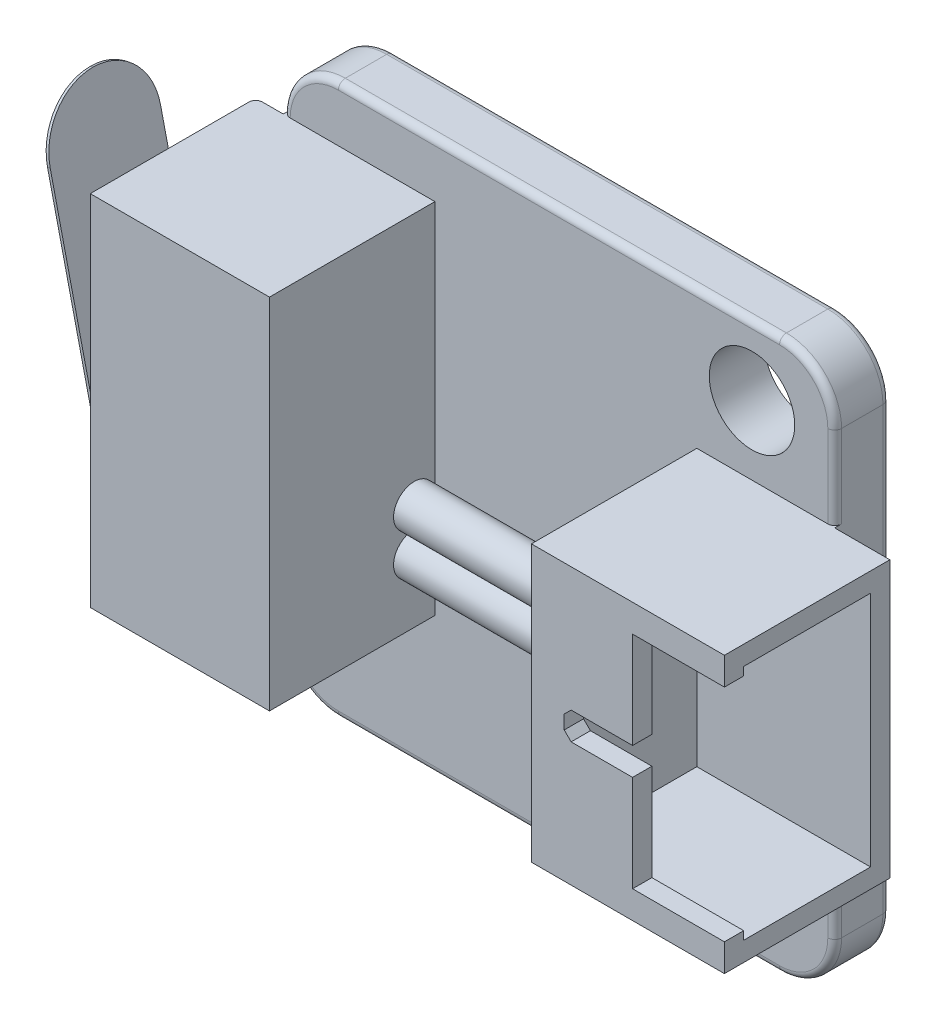
SolidWorks part; units mm, degrees
ref_plane "Alzado" through (0, 0, 0) normal (0, 0, 1) x (1, 0, 0)
ref_plane "Planta" through (0, 0, 0) normal (0, 1, 0) x (1, 0, 0)
ref_plane "Vista lateral" through (0, 0, 0) normal (1, 0, 0) x (0, 0, -1)
ref_plane "Plano1" through (0, 0, 2) normal (0, 0, 1) x (1, 0, 0)
sketch "Croquis1" plane through (0, 0, 2) normal (0, 0, 1) x (1, 0, 0)
  line L0 (-10, 10) -> (-10, -10)
  line L1 (-10, -10) -> (10, -10)
  line L2 (10, -10) -> (10, 10)
  line L3 (10, 10) -> (-10, 10)
extrude "Saliente-Extruir1" add sketch "Croquis1" against normal blind 2
sketch "Croquis2" plane through (0, 0, 2) normal (0, 0, 1) x (1, 0, 0)
  line L0 (12, 5) -> (12, -5)
  line L1 (12, -5) -> (5, -5)
  line L2 (5, -5) -> (5, 5)
  line L3 (5, 5) -> (12, 5)
extrude "Saliente-Extruir2" add sketch "Croquis2" along normal blind 6
sketch "Croquis3" plane through (0, 0, 2) normal (0, 0, 1) x (1, 0, 0)
  line L0 (-4.5, 8) -> (-4.5, -5)
  line L1 (-4.5, -5) -> (-11, -5)
  line L2 (-11, -5) -> (-11, 8)
  line L3 (-11, 8) -> (-4.5, 8)
extrude "Saliente-Extruir3" add sketch "Croquis3" along normal blind 6
ref_plane "Plano2" through (0, 0, 7) normal (0, 0, 1) x (1, 0, 0)
sketch "Croquis4" plane through (0, 0, 7) normal (0, 0, 1) x (1, 0, 0)
  line L0 (-68.4062, -3.5553) -> (-70.3333, -4)
  line L1 (-70.3333, -4) -> (-11, -4)
  line L2 (-11, -4) -> (-11, -3.5553)
  line L3 (-11, -3.5553) -> (-68.4062, -3.5553)
extrude "Saliente-Extruir4" add sketch "Croquis4" against normal blind 4
sketch "Croquis6" plane through (0, 0, 0) normal (0, 0, -1) x (-1, 0, 0)
  line L0 (1, 7.5) -> (4, 7.5)
  line L1 (4, 7.5) -> (4, -5)
  line L2 (4, -5) -> (1, -5)
  line L3 (1, -5) -> (1, 7.5)
extrude "Saliente-Extruir6" add sketch "Croquis6" along normal blind 2
sketch "Croquis7" plane through (0, 0, 0) normal (0, 0, -1) x (-1, 0, 0)
  line L0 (-6, 3.5) -> (-4, 3.5)
  line L1 (-4, 3.5) -> (-4, -3.5)
  line L2 (-4, -3.5) -> (-6, -3.5)
  line L3 (-6, -3.5) -> (-6, 3.5)
extrude "Saliente-Extruir7" add sketch "Croquis7" along normal blind 2
sketch "Croquis8" plane through (12, 0, 0) normal (1, 0, 0) x (0, 0, -1)
  line L0 (-2.7, 4.3) -> (-7.3, 4.3)
  line L1 (-7.3, 4.3) -> (-7.3, -4.3)
  line L2 (-7.3, -4.3) -> (-2.7, -4.3)
  line L3 (-2.7, -4.3) -> (-2.7, 4.3)
extrude "Cortar-Extruir1" cut sketch "Croquis8" against normal blind 6.3
draft "Ángulo de salida1" type of draft neutral plane draft angle 77.005 faces to draft 1 face at (-39.7031, -3.5553, 5) neutral plane through (-11, -5, 8) neutral plane normal (-1, 0, 0) reverse direction yes parameters "D1"=77.005
draft "Ángulo de salida2" type of draft neutral plane draft angle 77.005 faces to draft 1 face at (-40.6667, -4, 5) neutral plane through (-11, -5, 8) neutral plane normal (-1, 0, 0) parameters "D1"=77.005
ref_plane "Plano3" through (0, -1.5, 0) normal (0, 1, 0) x (1, 0, 0)
ref_plane "Plano4" through (0, 5, 0) normal (0, 1, 0) x (1, 0, 0)
ref_plane "Plano5" through (0, 4.5, 0) normal (0, -1, 0) x (1, 0, 0)
ref_plane "Plano6" through (0, -2.5, 0) normal (0, -1, 0) x (1, 0, 0)
hole_wizard "Diámetro de taladro Ø3.1 (3.1)1" positions "Croquis14" profile "Croquis13" hole size "Ø3.1" standard "Ansi Metric"
sketch "Croquis14" plane through (0, 0, 2) normal (0, 0, 1) x (1, 0, 0)
  point P0 (7, -7.5)
  point P1 (7, 7.5)
sketch "Croquis13" plane through (7, -7.5, 2) normal (1, 0, 0) x (0, -1, 0)
  line L0 (0, 0) -> (0, 4)
  line L1 (0, 4) -> (1.55, 4)
  line L2 (1.55, 4) -> (1.55, 0)
  line L5 (1.55, 0) -> (0, 0)
  line L11 (0, -6.35) -> (0, 107.95) construction
  dimension "Diámetro de taladro hasta el siguiente" = 3.1
  dimension "Profundidad de taladro hasta el siguiente" = 4
ref_plane "Plano7" through (0, 1.4209, 0) normal (0, 1, 0) x (1, 0, 0)
fillet "Redondeo2" radius 2 4 edges at (-10, 10, 1) (10, 10, 1) (10, -10, 1) (-10, -10, 1) tangent propagation no
fillet "Redondeo3" radius 2 2 edges at (-13.9513, 9.0112, 7) (-13.9513, 9.0112, 3)
fillet "Redondeo4" radius 0.25 18 edges at (9.4142, -9.4142, 0) (0, -10, 0) (-9.4142, -9.4142, 0) (-10, 0, 0) (-9.4142, 9.4142, 0) (0, 10, 0) (9.4142, 9.4142, 0) (10, 6.5, 2) (9.4142, 9.4142, 2) (0, 10, 2) (-10, -6.5, 2) (-9.4142, -9.4142, 2) (10, -6.5, 2) (9.4142, -9.4142, 2) (10, 0, 0) (-9.4142, 9.4142, 2) (-11, 1.5, 2) (0, -10, 2)
sketch "Croquis16" plane through (0, 0, 8) normal (0, 0, 1) x (1, 0, 0)
  line L0 (12, -4) -> (8.6692, -4)
  line L1 (12, -5) -> (12, 5) construction
  line L2 (8.6692, 4) -> (8.6692, 0.5)
  line L3 (12, 4) -> (12, -4)
  line L4 (8.6692, 0.5) -> (6.1906, 0.5)
  line L5 (8.6692, -0.5) -> (6.1906, -0.5)
  line L6 (6.1906, -0.5) -> (6.1906, 0.5)
  line L7 (8.6692, 4) -> (12, 4)
  line L8 (5.5, 5) -> (-5.5, 5) construction
  line L9 (5, -5) -> (12, -5) construction
  line L10 (8.6692, -0.5) -> (8.6692, -4)
  dimension "D1" = 1
  dimension "D2" = 1
extrude "Cortar-Extruir2" cut sketch "Croquis16" against normal blind 1
chamfer "Chaflán1" distance 0.25 angle 45 2 edges at (6.1906, -0.5, 7.65) (6.1906, 0.5, 7.65)
ref_plane "Plano8" through (0, 0, 2.5) normal (0, 0, 1) x (1, 0, 0)
sketch "Croquis19" plane through (-4.5, 0, 0) normal (1, 0, 0) x (0, 0, -1)
  line L0 (-2, -5) -> (-2, 8) construction
  circle A0 centre (-2.75, -2.6663) radius 0.75
  circle A1 centre (-2.75, -1.1663) radius 0.75
  dimension "D1" = 1.5
extrude "Saliente-Extruir9" add sketch "Croquis19" along direction (1, 0, 0) on the side of the normal blind 10 from surface separate body contours A1 | A0 region at (-4.5, -2.6663, 2.75) region at (-4.5, -1.1663, 2.75) starting at face at (-4.5, 1.5, 5)
